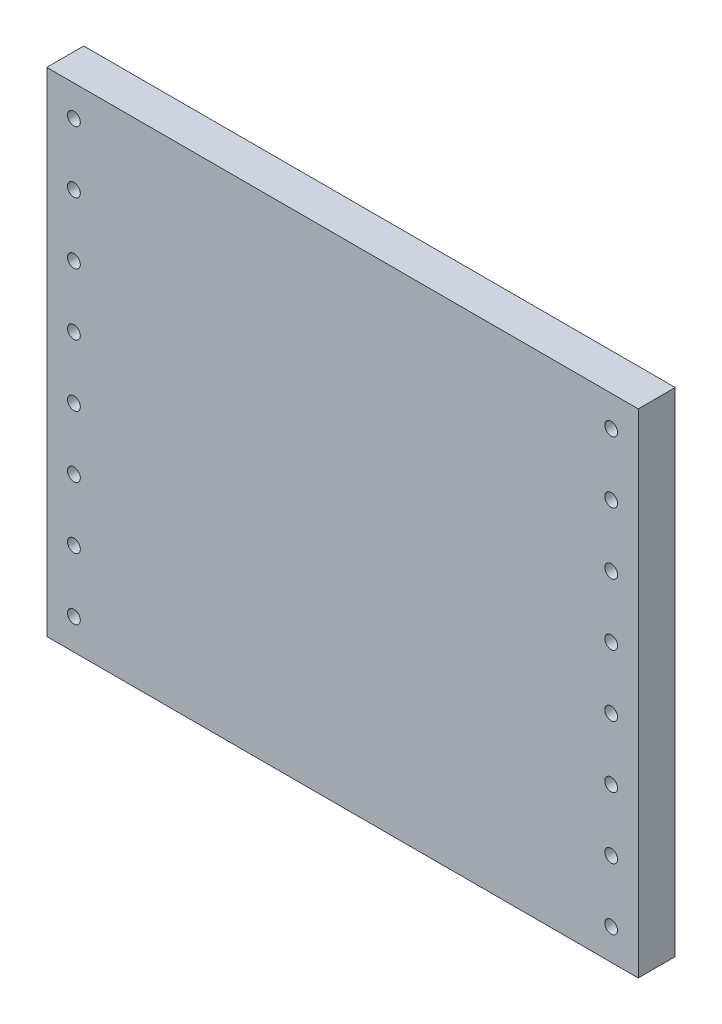
SolidWorks part; units mm, degrees
ref_plane "Front Plane" through (0, 0, 0) normal (0, 0, 1) x (1, 0, 0)
ref_plane "Top Plane" through (0, 0, 0) normal (0, 1, 0) x (1, 0, 0)
ref_plane "Right Plane" through (0, 0, 0) normal (1, 0, 0) x (0, 0, -1)
sketch "Sketch1" plane through (0, 0, 0) normal (0, 0, 1) x (1, 0, 0)
  line L1 (-120, -100) -> (120, -100)
  line L2 (-120, -100) -> (-120, 100)
  line L3 (-120, 100) -> (120, 100)
  line L4 (120, -100) -> (120, 100)
  line L5 (-120, -100) -> (120, 100) construction
  line L6 (-120, 100) -> (120, -100) construction
  point P0 (0, 0)
  dimension "D1" = 240
  dimension "D2" = 200
extrude "Boss-Extrude1" add sketch "Sketch1" along normal mid plane 15
sketch "Sketch4" plane through (0, 0, 7.5) normal (0, 0, 1) x (1, 0, 0)
  line L0 (-109, -1033.7087) -> (-109, 48966.2913) construction
  line L1 (109, -1052.3781) -> (109, 48947.6219) construction
  line L2 (-1012.9649, 87.5) -> (48987.0351, 87.5) construction
  line L4 (-120, 100) -> (-120, -100) construction
  line L5 (120, -100) -> (120, 100) construction
  line L6 (120, 100) -> (-120, 100) construction
  circle A0 centre (-109, 87.5) radius 2.6
  circle A1 centre (109, 87.5) radius 2.6
  dimension "D4" = 5.2
  dimension "D5" = 5.2
  dimension "D1" = 12.5
  dimension "D2" = 11
  dimension "D3" = 11
extrude "Cut-Extrude3" cut sketch "Sketch4" against normal through all
pattern_linear "LPattern1" count 8 spacing 25 along (0, -1, 0) of "Cut-Extrude3"
sketch "Sketch3" [suppressed] plane through (0, 7.5, 0) normal (0, 1, 0) x (1, 0, 0)
  line L1 (-92.5, -105) -> (92.5, -105)
  line L2 (-97.5, -100) -> (-97.5, 100)
  line L3 (-92.5, 105) -> (92.5, 105)
  line L4 (97.5, -100) -> (97.5, 100)
  line L5 (-97.5, -105) -> (97.5, 105) construction
  line L6 (-97.5, 105) -> (97.5, -105) construction
  arc A0 (-92.5, -105) -> (-97.5, -100) centre (-92.5, -100) cw
  arc A1 (97.5, -100) -> (92.5, -105) centre (92.5, -100) cw
  arc A2 (97.5, 100) -> (92.5, 105) centre (92.5, 100) ccw
  arc A3 (-92.5, 105) -> (-97.5, 100) centre (-92.5, 100) ccw
  point P0 (0, 0)
  dimension "D3" = 5
  dimension "D1" = 195
  dimension "D2" = 210
